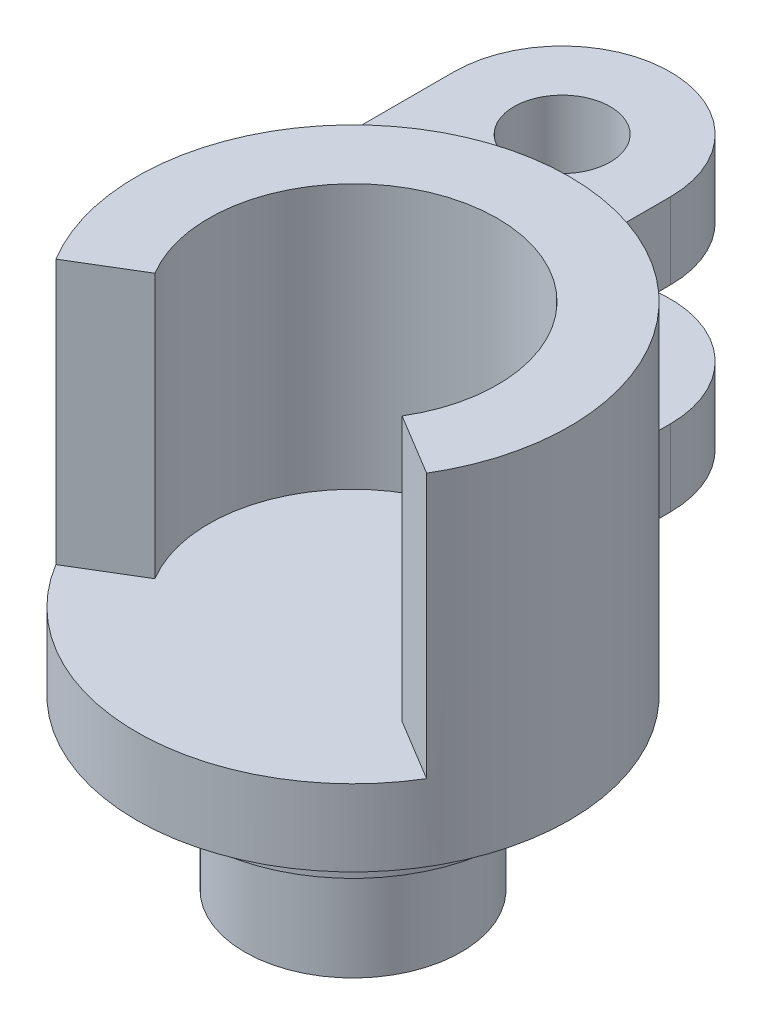
SolidWorks part; units mm, degrees
ref_plane "Front Plane" through (0, 0, 0) normal (0, 0, 1) x (1, 0, 0)
ref_plane "Top Plane" through (0, 0, 0) normal (0, 1, 0) x (1, 0, 0)
ref_plane "Right Plane" through (0, 0, 0) normal (1, 0, 0) x (0, 0, -1)
sketch "Sketch1" plane through (0, 0, 0) normal (0, 1, 0) x (1, 0, 0)
  circle A0 centre (0, 0) radius 9
  dimension "D1" = 18
extrude "Boss-Extrude1" add sketch "Sketch1" along normal blind 3.175
sketch "Sketch2" plane through (0, 3.175, 0) normal (0, 1, 0) x (1, 0, 0)
  line L0 (-7.7077, -4.6466) -> (-5.1385, -3.0978)
  line L1 (-7.7077, -4.6466) -> (7.7077, -4.6466) construction
  line L3 (5.1385, -3.0978) -> (7.7077, -4.6466)
  arc A0 (-7.7077, -4.6466) -> (7.7077, -4.6466) centre (0, 0) cw
  circle A1 centre (0, 0) radius 9 construction
  arc A2 (-5.1385, -3.0978) -> (5.1385, -3.0978) centre (0, 0) cw
  dimension "D1" = 117.832
  dimension "D2" = 3
extrude "Boss-Extrude2" add sketch "Sketch2" along normal blind 11
sketch "Sketch3" plane through (0, 0, 0) normal (0, -1, 0) x (1, 0, 0)
  circle A0 centre (0, 0) radius 6.5
  dimension "D1" = 13
extrude "Boss-Extrude3" add sketch "Sketch3" along normal blind 2
sketch "Sketch4" plane through (0, -2, 0) normal (0, -1, 0) x (1, 0, 0)
  circle A0 centre (0, 0) radius 4.5
  dimension "D1" = 9
extrude "Boss-Extrude4" add sketch "Sketch4" along normal blind 5
sketch "Sketch6" plane through (0, 0, 0) normal (0, 1, 0) x (1, 0, 0)
  line L0 (-9, 0) -> (-9, 13.1942)
  line L1 (0, 9) -> (0, 13.1942)
  arc A0 (7.7077, -4.6466) -> (-7.7077, -4.6466) centre (0, 0) ccw construction
  arc A1 (0, 13.1942) -> (-9, 13.1942) centre (-4.5, 13.1942) ccw
  arc A2 (0, 9) -> (-9, 0) centre (0, 0) ccw
  point P10 (-4.5, 17.6942)
  dimension "D1" = 8.6942
extrude "Boss-Extrude5" add sketch "Sketch6" along normal up to surface (3.175 mm away) up to face at (0, 3.175, 2.6861)
ref_plane "Plane1" through (0, 8.175, 0) normal (0, 1, 0) x (1, 0, 0)
sketch "Sketch7" plane through (0, 8.175, 0) normal (0, 1, 0) x (1, 0, 0)
  line L0 (0, 9) -> (0, 13.1942) construction
  line L1 (-9, 13.1942) -> (-9, 0) construction
  line L2 (0, 9) -> (0, 13.1942)
  line L3 (-9, 13.1942) -> (-9, 0)
  arc A0 (0, 9) -> (-9, 0) centre (0, 0) ccw construction
  arc A1 (0, 13.1942) -> (-9, 13.1942) centre (-4.5, 13.1942) ccw construction
  arc A2 (0, 9) -> (-9, 0) centre (0, 0) ccw
  arc A3 (0, 13.1942) -> (-9, 13.1942) centre (-4.5, 13.1942) ccw
extrude "Boss-Extrude7" add sketch "Sketch7" along normal blind 3.175
sketch "Sketch8" plane through (0, 11.35, 0) normal (0, 1, 0) x (1, 0, 0)
  circle A0 centre (-4.5, 13.1942) radius 2
  arc A1 (0, 13.1942) -> (-9, 13.1942) centre (-4.5, 13.1942) ccw construction
  dimension "D1" = 4
extrude "Cut-Extrude1" cut sketch "Sketch8" against normal up to surface (11.35 mm away) up to face at (0, 0, -6.5)
